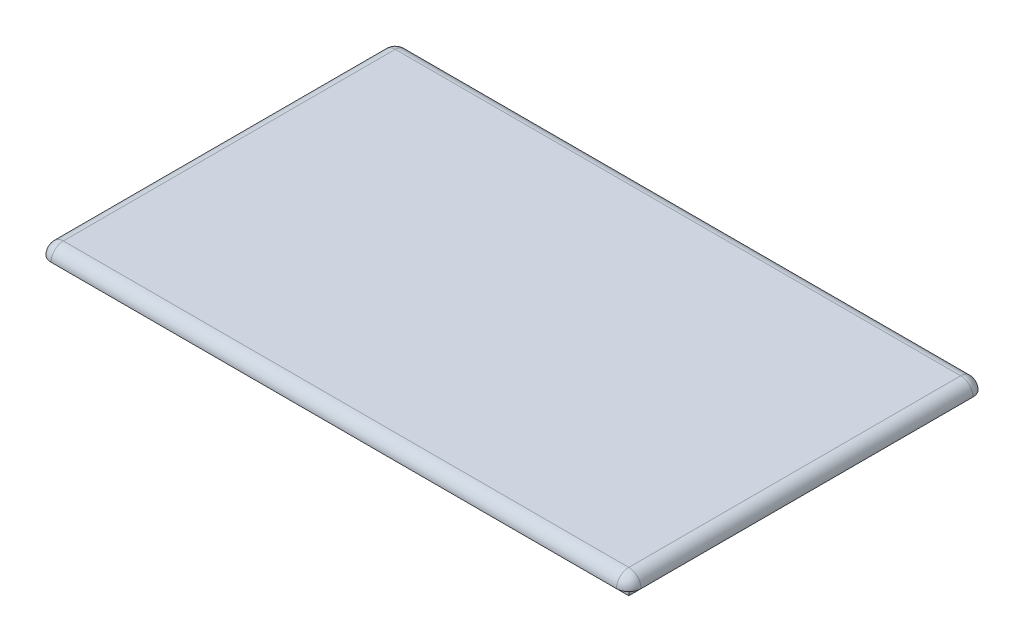
SolidWorks part; units mm, degrees
ref_plane "正面" through (0, 0, 0) normal (0, 0, 1) x (1, 0, 0)
ref_plane "平面" through (0, 0, 0) normal (0, 1, 0) x (1, 0, 0)
ref_plane "右側面" through (0, 0, 0) normal (1, 0, 0) x (0, 0, -1)
sketch "ｽｹｯﾁ1" plane through (0, 0, 0) normal (0, 1, 0) x (1, 0, 0)
  line L0 (-47.457, 36.7515) -> (-1.457, 36.7515)
  line L1 (-47.457, 36.7515) -> (-47.457, 9.7515)
  line L2 (-1.457, 36.7515) -> (-1.457, 9.7515)
  line L3 (-47.457, 9.7515) -> (-1.457, 9.7515)
  dimension "D1" = 46
  dimension "D2" = 27
extrude "ﾎﾞｽ - 押し出し1" add sketch "ｽｹｯﾁ1" along normal blind 1
sketch "ｽｹｯﾁ2" plane through (0, 1, 0) normal (0, 1, 0) x (1, 0, 0)
  line L0 (-48.457, 37.7515) -> (-0.457, 37.7515)
  line L1 (-48.457, 37.7515) -> (-48.457, 8.7515)
  line L2 (-0.457, 37.7515) -> (-0.457, 8.7515)
  line L3 (-48.457, 8.7515) -> (-0.457, 8.7515)
  line L6 (-47.457, 36.7515) -> (-47.457, 9.7515) construction
  line L7 (-1.457, 36.7515) -> (-47.457, 36.7515) construction
  point P4 (-24.457, 23.2515)
  point P8 (-24.457, 23.2515)
  dimension "D1" = 48
  dimension "D2" = 29
  dimension "D3" = 24
  dimension "D4" = 14.5
  dimension "D5" = 23
  dimension "D6" = 13.5
extrude "ﾎﾞｽ - 押し出し2" add sketch "ｽｹｯﾁ2" along normal blind 1
fillet "ﾌｨﾚｯﾄ1" radius 1 4 edges at (-24.457, 2, -8.7515) (-48.457, 2, -23.2515) (-24.457, 2, -37.7515) (-0.457, 2, -23.2515)
